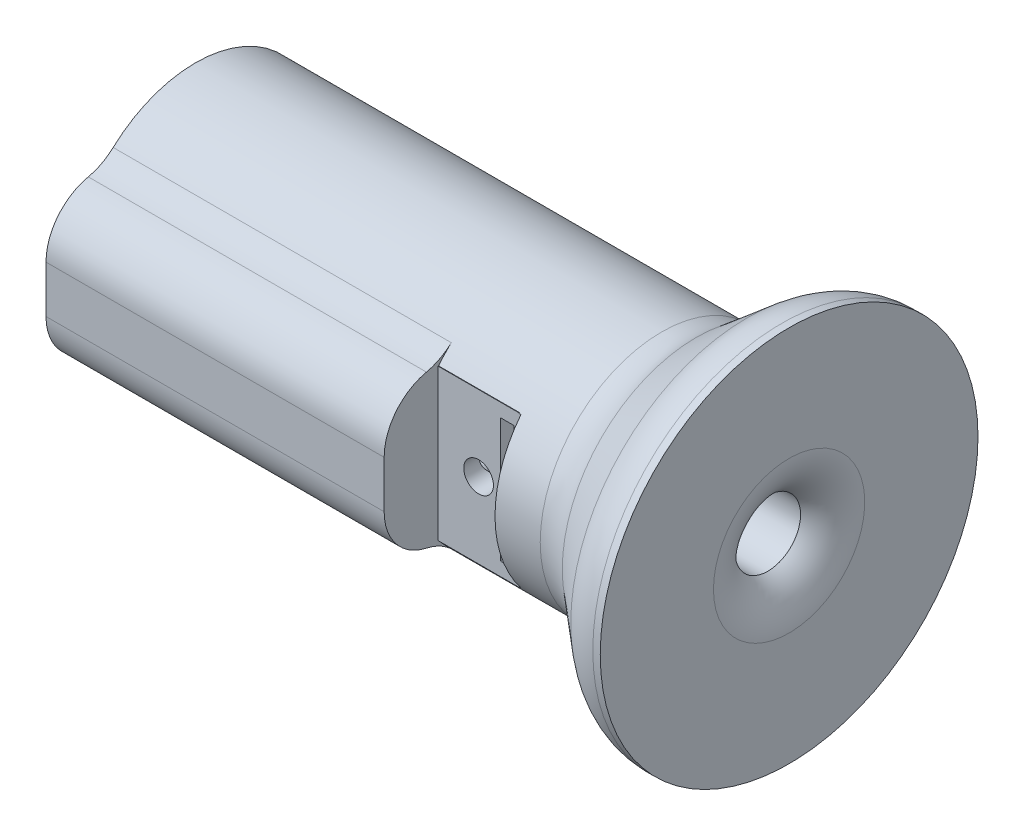
SolidWorks part; units mm, degrees
ref_plane "Piano frontale" through (0, 0, 0) normal (0, 0, 1) x (1, 0, 0)
ref_plane "Piano superiore" through (0, 0, 0) normal (0, 1, 0) x (1, 0, 0)
ref_plane "Piano destro" through (0, 0, 0) normal (1, 0, 0) x (0, 0, -1)
sketch "Schizzo2" plane through (0, 0, 0) normal (0, 1, 0) x (1, 0, 0)
  line L0 (-119.6897, 0) -> (125.4233, 0) construction
  line L1 (-91.7235, 22.5) -> (-91.7235, -22.5)
  line L4 (-1.7235, -22.5) -> (-91.7235, -22.5)
  line L5 (-91.7235, 22.5) -> (-1.7235, 22.5)
  line L6 (-1.7235, 22.5) -> (13.2765, 35)
  line L7 (-1.7235, -22.5) -> (13.2765, -35)
  line L8 (13.2765, -35) -> (18.2765, -35)
  line L9 (18.2765, -6.0616) -> (14.3354, -6.0616)
  line L10 (14.3354, -6.0616) -> (14.3354, 6.0616)
  line L11 (14.3354, 6.0616) -> (18.2765, 6.0616)
  line L12 (18.2765, 6.0616) -> (18.2765, 35)
  line L13 (18.2765, 35) -> (13.2765, 35)
  line L14 (18.2765, -35) -> (18.2765, -6.0616)
  point P12 (14.3354, 0)
  point P16 (-91.7235, 0)
  dimension "D1" = 45
  dimension "D2" = 90
  dimension "D3" = 70
  dimension "D4" = 5
revolve "Rivoluzione2" add sketch "Schizzo2" angle 360 about L0
sketch "Schizzo3" plane through (-91.7235, 0, 0) normal (-1, 0, 0) x (0, 0, 1)
  line L2 (17.7011, -15.4514) -> (26.9442, -15.4514)
  line L3 (17.7011, -15.4514) -> (17.7011, 15.4514)
  line L4 (17.7011, 15.4514) -> (26.9442, 15.4514)
  line L5 (26.9442, -15.4514) -> (26.9442, 15.4514)
  line L6 (17.7011, -15.4514) -> (26.9442, 15.4514) construction
  line L7 (17.7011, 15.4514) -> (26.9442, -15.4514) construction
extrude "Taglio-Estrusione2" cut sketch "Schizzo3" against normal blind 78 contours L5 L4 L3 L2
sketch "Schizzo4" plane through (0, 0, 17.7011) normal (0, 0, 1) x (1, 0, 0)
  line L3 (-14.0633, -14) -> (-29.0633, -14)
  line L4 (-14.0633, -14) -> (-14.0633, 14)
  line L5 (-14.0633, 14) -> (-29.0633, 14)
  line L6 (-29.0633, -14) -> (-29.0633, 14)
  line L7 (-14.0633, -14) -> (-29.0633, 14) construction
  line L8 (-14.0633, 14) -> (-29.0633, -14) construction
  point P5 (-21.5633, 0)
  dimension "D1" = 15
  dimension "D2" = 28
extrude "Estrusione-Estrusione1" add sketch "Schizzo4" against normal blind 12
hole_wizard "Foro per Vite M2-1" [suppressed] positions "Schizzo5" profile "Schizzo6" hole size "M2" standard "ISO"
sketch "Schizzo5" plane through (0, 0, 17.7011) normal (0, 0, 1) x (1, 0, 0)
  line L3 (-14.0633, 14) -> (-29.0633, 14) construction
  point P0 (-21.5633, 11.5)
  point P2 (-21.5633, -11.5)
  dimension "D1" = 2.5
sketch "Schizzo6" plane through (-21.5633, 11.5, 17.7011) normal (1, 0, 0) x (0, -1, 0)
  line L0 (0, 0) -> (0, 6.721)
  line L1 (0, 6.721) -> (1.2, 6)
  line L2 (1.2, 6) -> (1.2, 0)
  line L5 (1.2, 0) -> (0, 0)
  line L10 (0, 6.721) -> (-1.2, 6) construction
  line L11 (0, -6.35) -> (0, 107.95) construction
  dimension "Hole Dia." = 2.4
  dimension "Hole Depth" = 6
  dimension "Drill Angle" = 118
hole_wizard "Foro per Vite M4-2" positions "Schizzo12" profile "Schizzo10" hole size "M4" standard "ISO"
sketch "Schizzo12" plane through (-91.7235, 0, 0) normal (-1, 0, 0) x (0, 0, 1)
  point P0 (0, 0)
sketch "Schizzo10" plane through (-91.7235, 0, 0) normal (0, 1, 0) x (0, 0, 1)
  line L0 (0, 0) -> (0, 60)
  line L1 (0, 60) -> (18.5, 60)
  line L2 (18.5, 60) -> (18.5, 0)
  line L5 (18.5, 0) -> (0, 0)
  line L10 (0, 60) -> (-18.5, 60) construction
  line L11 (0, -6.35) -> (0, 107.95) construction
  dimension "Hole Dia." = 37
  dimension "Hole Depth" = 60
  dimension "Drill Angle" = 180
hole_wizard "Foro per Vite M5-1" positions "Schizzo13" profile "Schizzo14" hole size "M5" standard "ISO"
sketch "Schizzo13" plane through (0, 0, 17.7011) normal (0, 0, 1) x (1, 0, 0)
  line L0 (-21.5633, 14) -> (-21.5633, -14) construction
  line L1 (-14.0633, 14) -> (-29.0633, 14) construction
  line L2 (-29.0633, -14) -> (-14.0633, -14) construction
  point P0 (-21.5633, 0)
sketch "Schizzo14" plane through (-21.5633, 0, 17.7011) normal (1, 0, 0) x (0, -1, 0)
  line L0 (0, 0) -> (0, 10)
  line L1 (0, 10) -> (2.75, 10)
  line L2 (2.75, 10) -> (2.75, 0)
  line L5 (2.75, 0) -> (0, 0)
  line L10 (0, 10) -> (-2.75, 10) construction
  line L11 (0, -6.35) -> (0, 107.95) construction
  dimension "Hole Dia." = 5.5
  dimension "Hole Depth" = 10
  dimension "Drill Angle" = 180
hole_wizard "Foro per Vite M5-2" positions "Schizzo16" profile "Schizzo17" hole size "M5" standard "ISO"
sketch "Schizzo16" plane through (-31.7235, 0, 0) normal (-1, 0, 0) x (0, 0, 1)
  point P0 (12.0473, 0)
sketch "Schizzo17" plane through (-31.7235, 0, 12.0473) normal (0, 1, 0) x (0, 0, 1)
  line L0 (0, 0) -> (0, 10)
  line L1 (0, 10) -> (2.75, 10)
  line L2 (2.75, 10) -> (2.75, 0)
  line L5 (2.75, 0) -> (0, 0)
  line L10 (0, 10) -> (-2.75, 10) construction
  line L11 (0, -6.35) -> (0, 107.95) construction
  dimension "Hole Dia." = 5.5
  dimension "Hole Depth" = 10
  dimension "Drill Angle" = 180
hole_wizard "Foro per Vite M2-2" positions "Schizzo25" profile "Schizzo26" hole size "M2" standard "ISO"
sketch "Schizzo25" plane through (-91.7235, 0, 0) normal (-1, 0, 0) x (0, 0, 1)
  line L0 (0, 0) -> (0, -29.1712) construction
  line L2 (-4.2932, 0) -> (5.9973, 0) construction
  arc A0 (17.7011, 13.8896) -> (17.7011, -13.8896) centre (0, 0) ccw construction
  point P0 (0, 20.2)
  point P2 (0, -20.2)
  dimension "D1" = 20.2
sketch "Schizzo26" plane through (-91.7235, 20.2, 0) normal (0, 1, 0) x (0, 0, 1)
  line L0 (0, 0) -> (0, 4.721)
  line L1 (0, 4.721) -> (1.2, 4)
  line L2 (1.2, 4) -> (1.2, 0)
  line L5 (1.2, 0) -> (0, 0)
  line L10 (0, 4.721) -> (-1.2, 4) construction
  line L11 (0, -6.35) -> (0, 107.95) construction
  dimension "Hole Dia." = 2.4
  dimension "Hole Depth" = 4
  dimension "Drill Angle" = 118
ref_plane "Piano1" through (-14.0633, 14, 17.7011) normal (-1, 0, 0) x (0, 0, 1)
sketch "Schizzo28" plane through (0, 0, 17.7011) normal (0, 0, 1) x (1, 0, 0)
  line L1 (-29.0633, 13.8896) -> (-91.7235, 13.8896)
  line L2 (-29.0633, 13.8896) -> (-29.0633, -13.8896)
  line L3 (-29.0633, -13.8896) -> (-91.7235, -13.8896)
  line L4 (-91.7235, 13.8896) -> (-91.7235, -13.8896)
extrude "Estrusione-Estrusione7" add sketch "Schizzo28" along normal blind 10
sketch "Schizzo29" plane through (-91.7235, 0, 0) normal (-1, 0, 0) x (0, 0, 1)
  line L1 (17.7011, -5.3778) -> (26.549, -5.3778)
  line L2 (17.7011, -5.3778) -> (17.7011, 5.3778)
  line L3 (17.7011, 5.3778) -> (26.549, 5.3778)
  line L4 (26.549, -5.3778) -> (26.549, 5.3778)
  point P5 (17.7011, 5.3778)
extrude "Taglio-Estrusione5" cut sketch "Schizzo29" against normal blind 60
fillet "Raccordo20" radius 10 1 edges at (18.2765, 0, 6.0616)
fillet "Raccordo21" radius 10 1 edges at (13.2765, 0, 35)
fillet "Raccordo22" radius 10 1 edges at (-1.7235, 0, 22.5)
fillet "Raccordo24" radius 10 1 edges at (-60.3934, 13.8896, 17.7011)
fillet "Raccordo25" radius 10 1 edges at (-60.3934, 13.8896, 27.7011)
fillet "Raccordo26" radius 10 1 edges at (-60.3934, -13.8896, 17.7011)
fillet "Raccordo27" radius 10 1 edges at (-60.3934, -13.8896, 27.7011)
fillet "Raccordo29" [suppressed] radius 10
sketch "Schizzo30" plane through (14.3354, 0, 0) normal (1, 0, 0) x (0, 0, -1)
  circle A0 centre (0, 0) radius 6.0616
extrude "Taglio-Estrusione6" cut sketch "Schizzo30" against normal blind 23
sketch "Schizzo31" plane through (0, 0, 17.7011) normal (0, 0, 1) x (1, 0, 0)
  line L0 (-13.7235, 0) -> (-29.0633, 0) construction
  line L1 (-13.7235, -13.8896) -> (-13.7235, 13.8896) construction
  line L2 (-29.0633, 14) -> (-29.0633, -14) construction
  line L3 (-14.0633, 14) -> (-29.0633, 14) construction
  line L4 (-17.5185, 11.5) -> (-15.0185, 11.5)
  line L5 (-17.5185, 11.5) -> (-17.5185, -11.5)
  line L6 (-17.5185, -11.5) -> (-15.0185, -11.5)
  line L7 (-15.0185, 11.5) -> (-15.0185, -11.5)
  line L8 (-17.5185, 11.5) -> (-15.0185, -11.5) construction
  line L9 (-17.5185, -11.5) -> (-15.0185, 11.5) construction
  circle A0 centre (-21.5633, 0) radius 2.75 construction
  point P6 (-16.2685, 0)
  point P13 (-21.5633, 0)
  point P14 (-18.8133, 0)
  dimension "D1" = 2.5
  dimension "D2" = 2.545
  dimension "D3" = 2.5
extrude "Taglio-Estrusione7" cut sketch "Schizzo31" against normal blind 23.75 contours L7 L6 L5 L4
hole_wizard "Foro svasato per Vite M3-1" positions "Schizzo32" profile "Schizzo34" countersink size "M3" standard "ISO"
sketch "Schizzo32" plane through (-8.6646, 0, 0) normal (1, 0, 0) x (0, 0, -1)
  point P0 (0, 0)
sketch "Schizzo34" plane through (-8.6646, 0, 0) normal (0, 1, 0) x (0, 0, -1)
  line L0 (0, 0) -> (0, 24.0794)
  line L1 (0, 24.0794) -> (1.7, 23.0579)
  line L2 (1.7, 23.0579) -> (1.7, 1.45)
  line L3 (1.7, 1.45) -> (3.15, 0)
  line L5 (3.15, 0) -> (0, 0)
  line L6 (-1.7, 1.45) -> (-3.15, 0) construction
  line L10 (0, 24.0794) -> (-1.7, 23.0579) construction
  line L11 (0, -6.35) -> (0, 107.95) construction
  dimension "Hole Dia." = 3.4
  dimension "Hole Depth" = 23.0579
  dimension "Near C'Sink Dia." = 6.3
  dimension "Near C'Sink Angle" = 90
  dimension "Drill Angle" = 118
